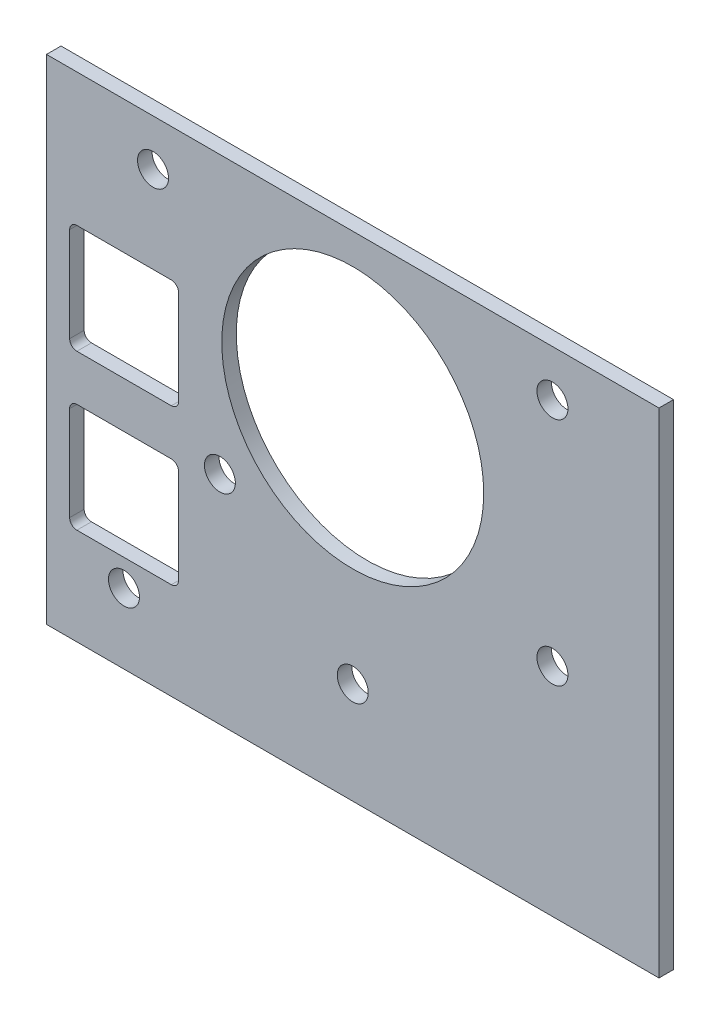
SolidWorks part; units mm, degrees
ref_plane "Front Plane" through (0, 0, 0) normal (0, 0, 1) x (1, 0, 0)
ref_plane "Top Plane" through (0, 0, 0) normal (0, 1, 0) x (1, 0, 0)
ref_plane "Right Plane" through (0, 0, 0) normal (1, 0, 0) x (0, 0, -1)
ref_plane "Plane1" through (0, 0, -1.0174) normal (0, 0, -1) x (-1, 0, 0)
sketch "Sketch1" plane through (0, 0, -1.0174) normal (0, 0, -1) x (-1, 0, 0)
  line L0 (118.3565, -137.9301) -> (124.8565, -137.9301)
  line L1 (125.3565, -138.4301) -> (125.3565, -144.9301)
  line L2 (124.8565, -145.4301) -> (118.3565, -145.4301)
  line L3 (117.8565, -144.9301) -> (117.8565, -138.4301)
  line L8 (124.8565, -156.0981) -> (118.3565, -156.0981)
  line L9 (117.8565, -155.5981) -> (117.8565, -149.0981)
  line L10 (118.3565, -148.5981) -> (124.8565, -148.5981)
  line L11 (125.3565, -149.0981) -> (125.3565, -155.5981)
  line L12 (117.8565, -141.6801) -> (125.3565, -141.6801) construction
  line L14 (126.9484, -128.7769) -> (84.7844, -128.7769)
  line L15 (121.6065, -148.5981) -> (121.6065, -156.0981) construction
  line L16 (121.6065, -156.0981) -> (121.6065, -152.3481) construction
  line L17 (121.6065, -152.3481) -> (125.3565, -152.3481) construction
  line L18 (126.9484, -128.7769) -> (126.9484, -162.7621)
  line L19 (126.9484, -162.7621) -> (84.7844, -162.7621)
  line L20 (84.7844, -128.7769) -> (84.7844, -162.7621)
  arc A0 (117.8565, -138.4301) -> (118.3565, -137.9301) centre (118.3565, -138.4301) cw
  arc A1 (124.8565, -137.9301) -> (125.3565, -138.4301) centre (124.8565, -138.4301) cw
  arc A2 (125.3565, -144.9301) -> (124.8565, -145.4301) centre (124.8565, -144.9301) cw
  arc A3 (118.3565, -145.4301) -> (117.8565, -144.9301) centre (118.3565, -144.9301) cw
  circle A4 centre (105.8664, -139.899) radius 9.017
  circle A5 centre (92.1183, -147.8365) radius 1.0668
  circle A6 centre (92.1183, -131.9615) radius 1.0668
  circle A7 centre (119.6146, -131.9615) radius 1.0668
  circle A8 centre (105.8664, -155.774) radius 1.0668
  circle A14 centre (115.0104, -147.8365) radius 1.0633
  circle A40 centre (121.6144, -157.933) radius 1.0668
  arc A43 (125.3565, -155.5981) -> (124.8565, -156.0981) centre (124.8565, -155.5981) cw
  arc A44 (118.3565, -156.0981) -> (117.8565, -155.5981) centre (118.3565, -155.5981) cw
  arc A45 (117.8565, -149.0981) -> (118.3565, -148.5981) centre (118.3565, -149.0981) cw
  arc A46 (124.8565, -148.5981) -> (125.3565, -149.0981) centre (124.8565, -149.0981) cw
  dimension "D1" = 33.9852
  dimension "D2" = 7.5
  dimension "D3" = 6.5
  dimension "D4" = 7.5
  dimension "D5" = 7.5
  dimension "D6" = 42.164
extrude "Boss-Extrude1" add sketch "Sketch1" against normal blind 1
